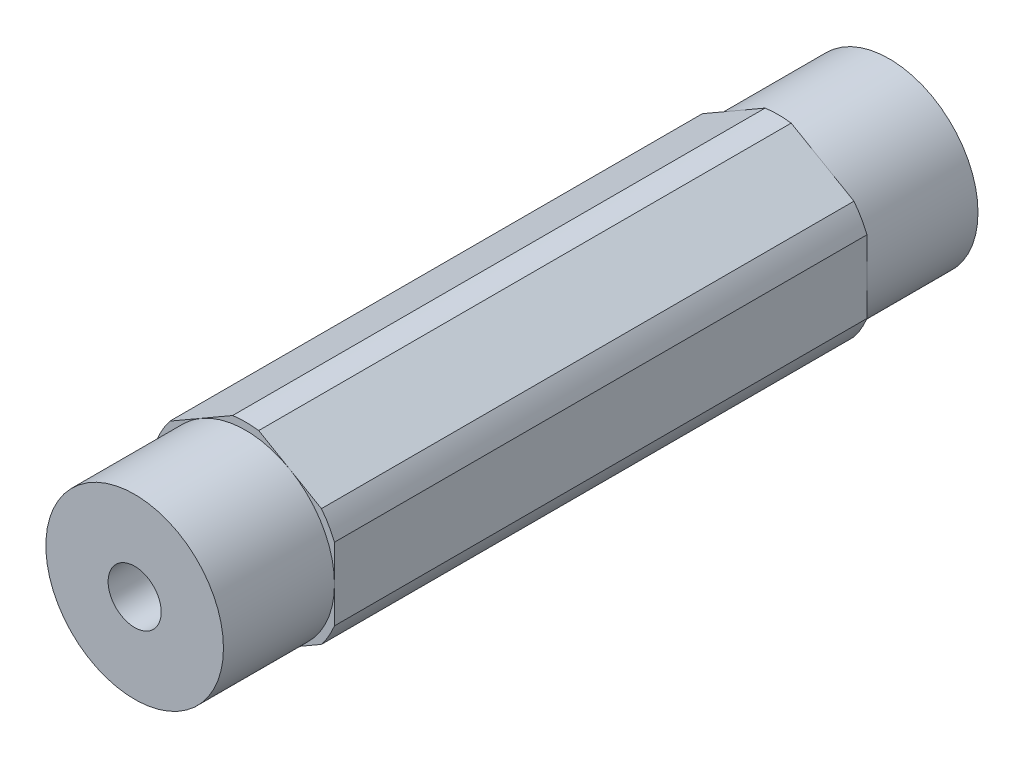
SolidWorks part; units mm, degrees
ref_plane "Front Plane" through (0, 0, 0) normal (0, 0, 1) x (1, 0, 0)
ref_plane "Top Plane" through (0, 0, 0) normal (0, 1, 0) x (1, 0, 0)
ref_plane "Right Plane" through (0, 0, 0) normal (1, 0, 0) x (0, 0, -1)
sketch "Sketch1" plane through (0, 0, 0) normal (0, 0, 1) x (1, 0, 0)
  line L1 (0, 7.3323) -> (-6.35, 3.6662)
  line L2 (-6.35, 3.6662) -> (-6.35, -3.6662)
  line L3 (-6.35, -3.6662) -> (0, -7.3323)
  line L4 (0, -7.3323) -> (6.35, -3.6662)
  line L5 (6.35, -3.6662) -> (6.35, 3.6662)
  line L6 (6.35, 3.6662) -> (0, 7.3323)
  circle A0 centre (0, 0) radius 6.35 construction
  circle A1 centre (0, 0) radius 6.858
  dimension "D1" = 12.7
  dimension "D2" = 13.716
extrude "Boss-Extrude1" add sketch "Sketch1" along normal mid plane 53.9496 contours L5 A1 L6 L1 L2 L3 L4 region at (0, 0, 0)
sketch "Sketch2" plane through (0, 0, 0) normal (0, 0, 1) x (1, 0, 0)
  circle A0 centre (0, 0) radius 6.35
  dimension "D1" = 12.7
extrude "Cut-Extrude-Thin1" cut sketch "Sketch2" against normal blind 7.9375 and the other way through all from surface thin starting at face at (0, 0, 26.9748) thin type one direction wall 2.54
extrude "Cut-Extrude-Thin2" cut sketch "Sketch2<2>" along normal blind 7.9375 from surface thin starting at face at (0, 0, -26.9748) thin type one direction wall 2.54
sketch "Sketch2<2>" plane through (0, 0, 0) normal (0, 0, 1) x (1, 0, 0) same geometry as "Sketch2"
hole_wizard "#10-24 Tapped Hole1" positions "3DSketch1" profile "Sketch3" tap size "#10-24" standard "ANSI Inch"
sketch3d "3DSketch1"
  line L0 (0, 0, 26.9748) -> (0, 0, 19.0373) construction
  line L1 (0, 0, -19.0373) -> (0, 0, -26.9748) construction
  point P0 (0, 0, 26.9748)
  point P4 (0, 0, -26.9748)
sketch "Sketch3" plane through (0, 0, 26.9748) normal (1, 0, 0) x (0, -1, 0)
  line L0 (0, 0) -> (0, 13.0788)
  line L1 (0, 13.0788) -> (1.8986, 11.938)
  line L2 (1.8986, 11.938) -> (1.8986, 0)
  line L5 (1.8986, 0) -> (0, 0)
  line L10 (0, 13.0788) -> (-1.8987, 11.938) construction
  line L11 (0, -6.35) -> (0, 107.95) construction
  dimension "Tap Drill Dia." = 3.7973
  dimension "Tap Drill Depth" = 11.938
  dimension "Drill Angle" = 118
